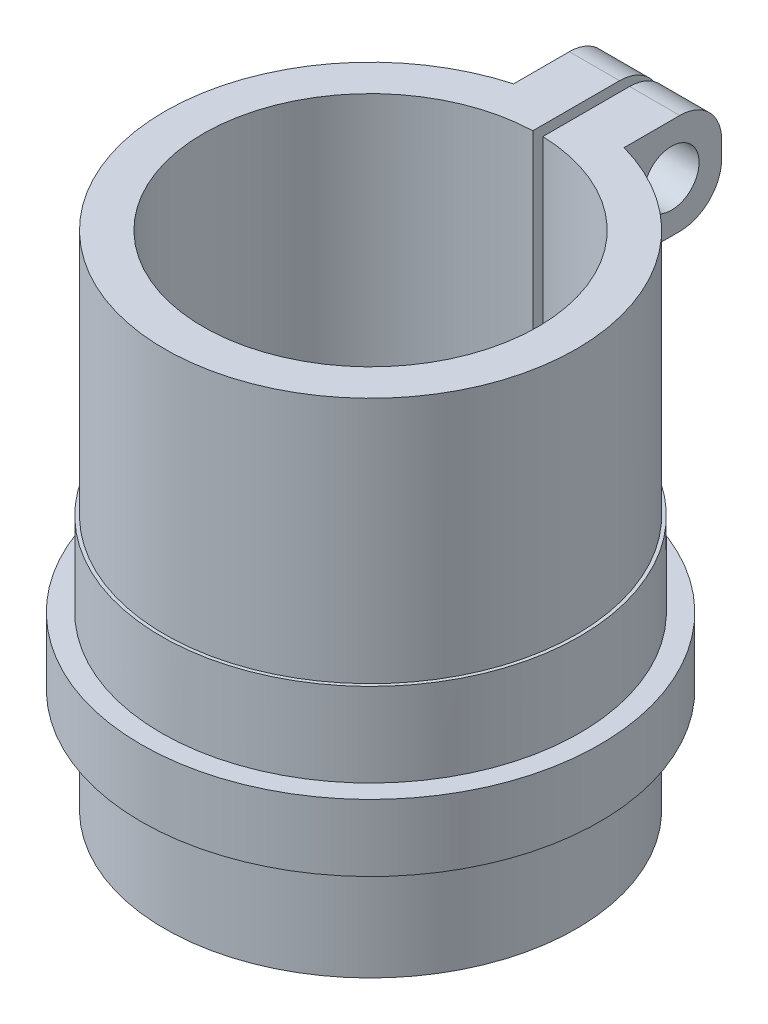
SolidWorks part; units mm, degrees
ref_plane "Front Plane" through (0, 0, 0) normal (0, 0, 1) x (1, 0, 0)
ref_plane "Top Plane" through (0, 0, 0) normal (0, 1, 0) x (1, 0, 0)
ref_plane "Right Plane" through (0, 0, 0) normal (1, 0, 0) x (0, 0, -1)
sketch "Sketch1" plane through (0, 0, 0) normal (0, 1, 0) x (1, 0, 0)
  circle A0 centre (0, 0) radius 15.875
  circle A1 centre (0, 0) radius 12.7
  dimension "D1" = 31.75
  dimension "D2" = 25.4
extrude "Boss-Extrude1" add sketch "Sketch1" along normal blind 38.1
ref_plane "Plane1" through (0, 7.9248, 0) normal (0, -1, 0) x (-1, 0, 0)
sketch "Sketch2" plane through (0, 7.9248, 0) normal (0, -1, 0) x (-1, 0, 0)
  circle A0 centre (0, 0) radius 15.875 construction
  circle A1 centre (0, 0) radius 15.875
  circle A2 centre (0, 0) radius 17.399
  dimension "D1" = 1.524
extrude "Boss-Extrude2" add sketch "Sketch2" against normal blind 5.0673
sketch "Sketch3" plane through (0, 0, 0) normal (0, -1, 0) x (1, 0, 0)
  circle A0 centre (0, 0) radius 15.621
  circle A1 centre (0, 0) radius 15.875 construction
  circle A2 centre (0, 0) radius 15.875
  dimension "D1" = 0.254
extrude "Cut-Extrude1" cut sketch "Sketch3" against normal up to surface (7.9248 mm away) up to face at (0, 7.9248, -15.875)
extrude "Cut-Extrude2" cut sketch "Sketch3<2>" along normal offset from surface (18.7579 mm away) 6.35 from surface up to face at (0, 12.9921, -15.875) starting at face at (0, 38.1, 15.875)
sketch "Sketch3<2>" plane through (0, 0, 0) normal (0, -1, 0) x (1, 0, 0) same geometry as "Sketch3"
sketch "Sketch4" plane through (0, 38.1, 0) normal (0, 1, 0) x (1, 0, 0)
  line L1 (-0.381, 12.6943) -> (0.381, 12.6943)
  line L2 (-0.381, 12.6943) -> (-0.381, 17.399)
  line L3 (-0.381, 17.399) -> (0.381, 17.399)
  line L4 (0.381, 12.6943) -> (0.381, 17.399)
  line L5 (-0.381, 12.6943) -> (0.381, 17.399) construction
  line L6 (-0.381, 17.399) -> (0.381, 12.6943) construction
  circle A0 centre (0, 0) radius 12.7 construction
  circle A1 centre (0, 0) radius 17.399 construction
  point P0 (0, 15.0466)
  point P5 (0, 0)
  point P9 (0, 0)
  point P10 (0, 12.7)
  point P11 (4.0292, 12.0439)
  dimension "D1" = 0.762
extrude "Cut-Extrude3" cut sketch "Sketch4" against normal blind 19.05
sketch "Sketch5" plane through (0.381, 0, 0) normal (-1, 0, 0) x (0, 0, 1)
  line L1 (-12.6943, 38.1) -> (-22.4518, 38.1)
  line L2 (-12.6943, 38.1) -> (-12.6943, 30.48)
  line L3 (-12.6943, 30.48) -> (-22.4518, 30.48)
  line L4 (-22.4518, 38.1) -> (-22.4518, 30.48)
  line L5 (-16.6211, 37.79) -> (-20.6625, 37.79) construction
  line L6 (-20.6625, 37.79) -> (-22.6833, 34.29) construction
  line L7 (-22.6833, 34.29) -> (-20.6625, 30.79) construction
  line L8 (-20.6625, 30.79) -> (-16.6211, 30.79) construction
  line L9 (-16.6211, 30.79) -> (-14.6004, 34.29) construction
  line L10 (-14.6004, 34.29) -> (-16.6211, 37.79) construction
  line L11 (-18.6418, 34.29) -> (-18.6418, 38.1) construction
  line L12 (-18.6418, 34.29) -> (-18.6418, 30.48) construction
  line L13 (-18.6418, 34.29) -> (-22.4518, 34.29) construction
  line L14 (-15.6164, 19.3421) -> (-15.6164, 38.1) construction
  circle A0 centre (-18.6418, 34.29) radius 2.1
  circle A1 centre (-18.6418, 34.29) radius 3.5 construction
  circle A2 centre (-18.6418, 34.29) radius 3.5 construction
  point P16 (-14.8761, 34.29)
  dimension "D1" = 4.2
  dimension "D3" = 7
  dimension "D2" = 3.81
  dimension "D4" = 1.016
extrude "Boss-Extrude3" add sketch "Sketch5" against normal blind 3.81
mirror "Mirror1" about plane through (0, 0, 0) normal (1, 0, 0) of "Boss-Extrude3"
fillet "Fillet1" radius 3.175 4 edges at (-2.286, 30.48, -22.4518) (2.286, 30.48, -22.4518) (2.286, 38.1, -22.4518) (-2.286, 38.1, -22.4518)
